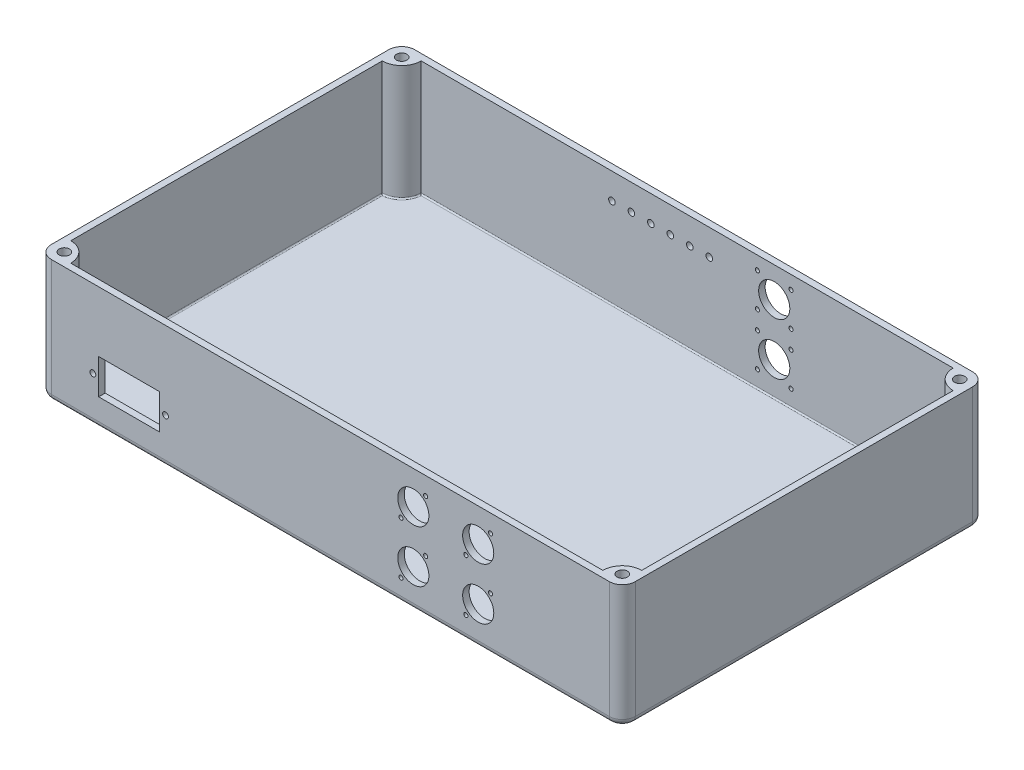
SolidWorks part; units mm, degrees
material "PMMA"
ref_plane "Front Plane" through (0, 0, 0) normal (0, 0, 1) x (1, 0, 0)
ref_plane "Top Plane" through (0, 0, 0) normal (0, 1, 0) x (1, 0, 0)
ref_plane "Right Plane" through (0, 0, 0) normal (1, 0, 0) x (0, 0, -1)
sketch "Sketch1" plane through (0, 0, 0) normal (0, 1, 0) x (1, 0, 0)
  line L1 (-225, 140) -> (225, 140)
  line L2 (-225, 140) -> (-225, -140)
  line L3 (-225, -140) -> (225, -140)
  line L4 (225, 140) -> (225, -140)
  line L5 (-225, 140) -> (225, -140) construction
  line L6 (-225, -140) -> (225, 140) construction
  point P0 (0, 0)
  dimension "D1" = 280
  dimension "D2" = 450
extrude "Boss-Extrude1" add sketch "Sketch1" along normal blind 95
fillet "Fillet1" radius 10 4 edges at (-225, 47.5, -140) (225, 47.5, -140) (225, 47.5, 140) (-225, 47.5, 140)
fillet "Fillet2" radius 5 8 edges at (-222.0711, 0, -137.0711) (0, 0, -140) (222.0711, 0, -137.0711) (225, 0, 0) (222.0711, 0, 137.0711) (0, 0, 140) (-222.0711, 0, 137.0711) (-225, 0, 0)
sketch "Sketch3" plane through (0, 95, 0) normal (0, 1, 0) x (1, 0, 0)
  line L0 (215, 135) -> (-215, 135)
  line L1 (-220, 130) -> (-220, -130)
  line L2 (-215, -135) -> (215, -135)
  line L3 (220, -130) -> (220, 130)
  line L4 (215, 140) -> (-215, 140)
  line L5 (-225, 130) -> (-225, -130)
  line L6 (-215, -140) -> (215, -140)
  line L7 (225, -130) -> (225, 130)
  line L8 (215, 140) -> (-215, 140)
  line L9 (-225, 130) -> (-225, -130)
  line L10 (-215, -140) -> (215, -140)
  line L11 (225, -130) -> (225, 130)
  arc A0 (-215, 135) -> (-220, 130) centre (-215, 130) ccw
  arc A1 (-220, -130) -> (-215, -135) centre (-215, -130) ccw
  arc A2 (215, -135) -> (220, -130) centre (215, -130) ccw
  arc A3 (220, 130) -> (215, 135) centre (215, 130) ccw
  arc A4 (-215, 140) -> (-225, 130) centre (-215, 130) ccw
  arc A5 (-225, -130) -> (-215, -140) centre (-215, -130) ccw
  arc A6 (215, -140) -> (225, -130) centre (215, -130) ccw
  arc A7 (225, 130) -> (215, 140) centre (215, 130) ccw
  arc A8 (-215, 140) -> (-225, 130) centre (-215, 130) ccw
  arc A9 (-225, -130) -> (-215, -140) centre (-215, -130) ccw
  arc A10 (215, -140) -> (225, -130) centre (215, -130) ccw
  arc A11 (225, 130) -> (215, 140) centre (215, 130) ccw
  dimension "D1" = 0
  dimension "D2" = 5
extrude "Cut-Extrude1" cut sketch "Sketch3" against normal offset from surface (89 mm away) 6 contours L3 A3 L0 A0 L1 A1 L2 A2 region at (0, 95, 0) up to face at (0, 0, 0)
sketch "Sketch5" plane through (0, 95, 0) normal (0, 1, 0) x (1, 0, 0)
  line L0 (215, 135) -> (-215, 135) construction
  line L1 (-220, 130) -> (-220, -130) construction
  line L2 (-205, 135) -> (-215, 135)
  line L3 (-220, 130) -> (-220, 120)
  arc A0 (-215, 135) -> (-220, 130) centre (-215, 130) ccw construction
  arc A1 (-215, 135) -> (-220, 130) centre (-215, 130) ccw
  arc A2 (-220, 120) -> (-205, 135) centre (-220, 135) ccw
  point P5 (-220, 120)
  point P6 (-205, 135)
  dimension "D1" = 10
  dimension "D2" = 10
extrude "Boss-Extrude2" add sketch "Sketch5" against normal up to next
mirror "Mirror1" about plane through (0, 0, 0) normal (0, 0, 1) of "Boss-Extrude2"
mirror "Mirror2" about plane through (0, 0, 0) normal (1, 0, 0) of "Mirror1"
fillet "Fillet4" radius 1 8 edges at (209.3934, 6, 124.3934) (0, 6, 135) (-209.3934, 6, 124.3934) (-220, 6, 0) (-209.3934, 6, -124.3934) (0, 6, -135) (209.3934, 6, -124.3934) (220, 6, 0)
sketch "Sketch7" plane through (0, 95, 0) normal (0, 1, 0) x (1, 0, 0)
  circle A0 centre (-215, 130) radius 4
  dimension "D1" = 8
extrude "Cut-Extrude2" cut sketch "Sketch7" against normal blind 40
mirror "Mirror3" about plane through (0, 0, 0) normal (0, 0, 1) of "Cut-Extrude2"
mirror "Mirror4" about plane through (0, 0, 0) normal (1, 0, 0) of "Mirror3"
sketch "Sketch8" plane through (0, 0, 140) normal (0, 0, 1) x (1, 0, 0)
  line L0 (-205, 7) -> (-205, 95) construction
  line L1 (205, 7) -> (205, 95) construction
  line L2 (-205, 7) -> (-205, 95)
  line L3 (205, 7) -> (205, 95)
  line L4 (-205, 35) -> (83.0015, 35) construction
  line L5 (-155, 48.45) -> (-155, 21.55) construction
  line L6 (-178.5, 48.45) -> (-131.5, 48.45)
  line L7 (-178.5, 48.45) -> (-178.5, 21.55)
  line L8 (-178.5, 21.55) -> (-131.5, 21.55)
  line L9 (-131.5, 48.45) -> (-131.5, 21.55)
  line L10 (-215, 5) -> (215, 5) construction
  circle A0 centre (-183, 35) radius 2.25
  circle A1 centre (-127, 35) radius 2.25
  point P10 (-178.5, 35)
  dimension "D3" = 4.5
  dimension "D4" = 4.5
  dimension "D5" = 28
  dimension "D1" = 26.9
  dimension "D2" = 47
  dimension "D6" = 28
  dimension "D7" = 30
  dimension "D8" = 50
extrude "Cut-Extrude3" cut sketch "Sketch8" against normal blind 10 contours A0 | A1 | L9 L6 L7 L8 region at (-155, 35, 140) region at (-183, 35, 140) region at (-127, 35, 140)
sketch "Sketch10" plane through (0, 0, -140) normal (0, 0, -1) x (-1, 0, 0)
  line L0 (-205, 7) -> (-205, 95) construction
  line L1 (205, 7) -> (205, 95) construction
  line L2 (-205, 7) -> (-205, 95)
  line L3 (205, 7) -> (205, 95)
  line L4 (-215, 95) -> (215, 95) construction
  line L6 (-17, 75) -> (171.729, 75) construction
  line L7 (225, 95) -> (225, 5) construction
  circle A0 centre (-17, 75) radius 2.53
  circle A1 centre (-2, 75) radius 2.53
  circle A2 centre (13, 75) radius 2.53
  circle A3 centre (28, 75) radius 2.53
  circle A4 centre (43, 75) radius 2.53
  circle A5 centre (58, 75) radius 2.53
  dimension "D5" = 242
  dimension "D2" = 5.06
  dimension "D3" = 6
  dimension "D4" = 15
  dimension "D1" = 20
extrude "Slots for LEDs" cut sketch "Sketch10" against normal blind 10 contours A3 L6 | L6 A3 | A4 L6 | L6 A4 | A5 L6 | L6 A5 | A2 | A1 | A0 region at (-58, 76.0738, -140) region at (-58, 73.9262, -140) region at (-43, 76.0738, -140) region at (-43, 73.9262, -140) region at (-28, 76.0738, -140) region at (-28, 73.9262, -140)
sketch "Sketch11" plane through (0, 0, 140) normal (0, 0, 1) x (1, 0, 0)
  line L0 (63.9557, 88.3373) -> (63.9557, 33.8229) construction
  line L1 (36.6203, 69.394) -> (109.1142, 69.394) construction
  line L2 (35.4029, 29.394) -> (139.3778, 29.394) construction
  line L3 (113.9557, 90.4744) -> (113.9557, 11.2015) construction
  circle A0 centre (63.9557, 69.394) radius 12
  circle A1 centre (73.4557, 41.394) radius 1.6
  circle A2 centre (54.4557, 17.394) radius 1.6
  circle A4 centre (113.9557, 69.394) radius 12
  circle A7 centre (113.9557, 29.394) radius 12
  circle A10 centre (63.9557, 29.394) radius 12
  circle A12 centre (73.4557, 81.394) radius 1.6
  circle A13 centre (54.4557, 57.394) radius 1.6
  circle A14 centre (123.4557, 41.394) radius 1.6
  circle A15 centre (104.4557, 17.394) radius 1.6
  circle A16 centre (123.4557, 81.394) radius 1.6
  circle A17 centre (104.4557, 57.394) radius 1.6
  dimension "D1" = 24
  dimension "D8" = 2
  dimension "D9" = 2
extrude "Cut-Extrude4" cut sketch "Sketch11" against normal blind 10
sketch "Sketch12" plane through (0, 0, -140) normal (0, 0, -1) x (-1, 0, 0)
  line L0 (-67.0784, 88.936) -> (-67.0784, 42.4939) construction
  line L1 (-94.7349, 71.7628) -> (-24.2141, 71.7628) construction
  circle A0 centre (-67.0784, 71.7628) radius 12
  circle A1 centre (-80.0784, 84.7628) radius 1.6
  circle A2 centre (-54.0784, 58.7628) radius 1.6
  circle A3 centre (-80.0784, 44.7628) radius 1.6
  circle A4 centre (-67.0784, 31.7628) radius 12
  circle A5 centre (-54.0784, 18.7628) radius 1.6
  circle A6 centre (-54.0784, 84.7628) radius 1.6
  circle A7 centre (-80.0784, 58.7628) radius 1.6
  circle A8 centre (-54.0784, 44.7628) radius 1.6
  circle A9 centre (-80.0784, 18.7628) radius 1.6
  dimension "D1" = 24
  dimension "D2" = 3.2
  dimension "D3" = 3.2
  dimension "D5" = 13
  dimension "D6" = 13
  dimension "D7" = 13
  dimension "D4" = 13
  dimension "D8" = 2
extrude "Cut-Extrude5" cut sketch "Sketch12" against normal blind 10
